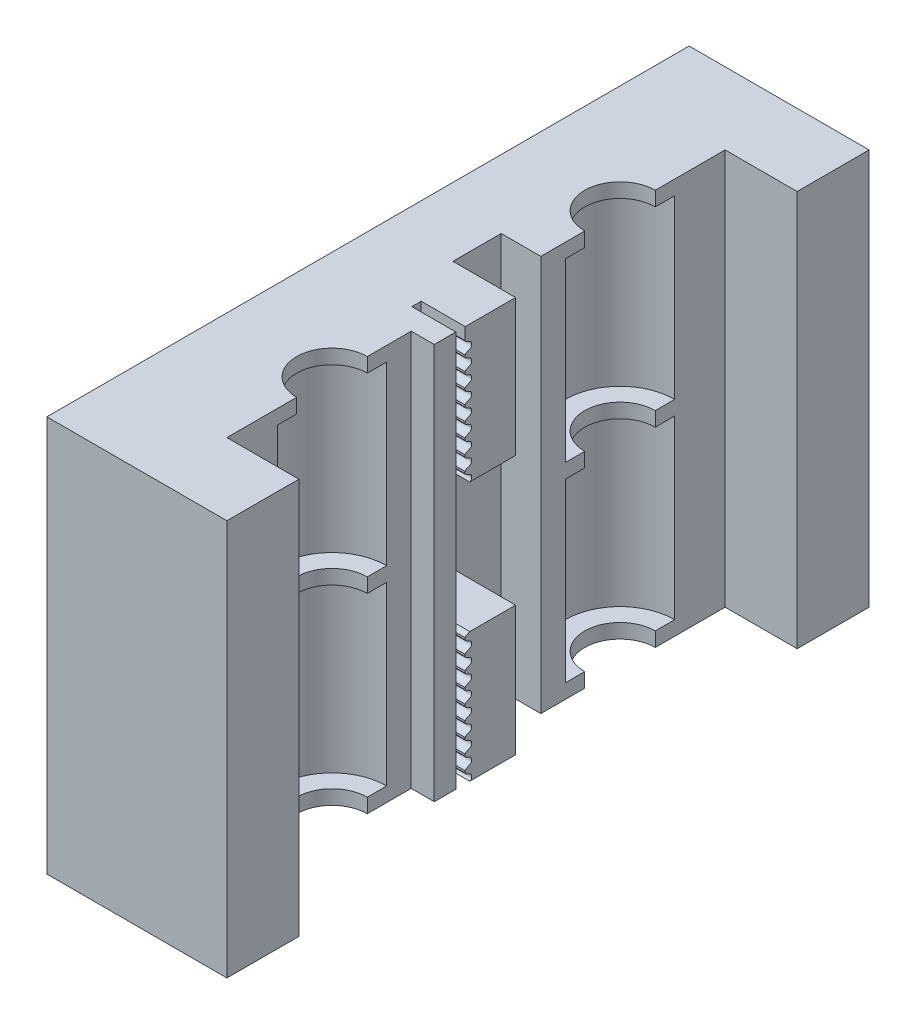
SolidWorks part; units mm, degrees
ref_plane "Front Plane" through (0, 0, 0) normal (0, 0, 1) x (1, 0, 0)
ref_plane "Top Plane" through (0, 0, 0) normal (0, 1, 0) x (1, 0, 0)
ref_plane "Right Plane" through (0, 0, 0) normal (1, 0, 0) x (0, 0, -1)
sketch "Sketch1" plane through (0, 0, 0) normal (0, 1, 0) x (1, 0, 0)
  line L0 (0, 36.6) -> (0, 43.6)
  line L1 (0, 43.6) -> (10, 43.6)
  line L2 (10, 43.6) -> (10, 53.6)
  line L3 (10, 53.6) -> (-15, 53.6)
  line L5 (-15, -35.6) -> (10, -35.6)
  line L6 (10, -35.6) -> (10, -25.6)
  line L7 (10, -25.6) -> (0, -25.6)
  line L8 (0, -25.6) -> (0, -18.6)
  line L9 (0, 21.4) -> (0, -3.4) construction
  line L10 (0, 18) -> (-5.5, 18)
  line L11 (-5.5, 18) -> (-5.5, 0)
  line L12 (-5.5, 0) -> (0, 0)
  line L24 (-15, 53.6) -> (-15, -35.6)
  line L25 (0, 0) -> (0, -3.4)
  line L26 (0, 18) -> (0, 21.4)
  arc A1 (0, 21.4) -> (0, 36.6) centre (0, 29) cw
  arc A2 (0, -18.6) -> (0, -3.4) centre (0, -11) cw
  dimension "D2" = 7.6
  dimension "D3" = 7.6
  dimension "D4" = 7
  dimension "D5" = 7
  dimension "D6" = 10
  dimension "D7" = 10
  dimension "D8" = 18
  dimension "D9" = 10
  dimension "D10" = 10
  dimension "D11" = 5.5
  dimension "D12" = 3.4
  dimension "D13" = 3.4
  dimension "D14" = 25
  dimension "D15" = 40
extrude "Boss-Extrude1" add sketch "Sketch1" along normal blind 55
sketch "Sketch2" plane through (0, 0, 0) normal (0, -1, 0) x (1, 0, 0)
  line L0 (0, 18.6) -> (0, 15.9)
  line L1 (0, 6.1) -> (0, 3.4)
  line L2 (0, -21.4) -> (0, -24.102)
  line L3 (0, -33.898) -> (0, -36.6)
  arc A0 (0, 3.4) -> (0, 18.6) centre (0, 11) cw
  arc A1 (0, 6.1) -> (0, 15.9) centre (0, 11) cw
  arc A2 (0, -36.6) -> (0, -21.4) centre (0, -29) cw
  arc A3 (0, -33.898) -> (0, -24.102) centre (0, -29) cw
  dimension "D1" = 4.9
  dimension "D2" = 4.898
extrude "Boss-Extrude2" add sketch "Sketch2" against normal blind 2
ref_plane "Plane1" through (0, 26.5, 0) normal (0, -1, 0) x (-1, 0, 0)
sketch "Sketch3" plane through (0, 26.5, 0) normal (0, -1, 0) x (-1, 0, 0)
  line L0 (0, -3.4) -> (0, -6.1)
  line L1 (0, -15.9) -> (0, -18.6)
  line L2 (0, 21.4) -> (0, 24.1)
  line L3 (0, 33.9) -> (0, 36.6)
  arc A0 (0, -18.6) -> (0, -3.4) centre (0, -11) ccw
  arc A1 (0, -15.9) -> (0, -6.1) centre (0, -11) ccw
  arc A2 (0, 36.6) -> (0, 21.4) centre (0, 29) cw
  arc A3 (0, 24.1) -> (0, 33.9) centre (0, 29) ccw
  dimension "D1" = 4.9
extrude "Boss-Extrude3" add sketch "Sketch3" against normal blind 2
ref_plane "Plane2" through (0, 53, 0) normal (0, -1, 0) x (-1, 0, 0)
sketch "Sketch4" plane through (0, 53, 0) normal (0, -1, 0) x (-1, 0, 0)
  line L0 (0, -18.6) -> (0, -15.9)
  line L1 (0, -6.1) -> (0, -3.4)
  line L2 (0, 36.6) -> (0, 33.9)
  line L3 (0, 24.1) -> (0, 21.4)
  arc A0 (0, -3.4) -> (0, -18.6) centre (0, -11) cw
  arc A1 (0, -15.9) -> (0, -6.1) centre (0, -11) ccw
  arc A2 (0, -15.9) -> (0, -6.1) centre (0, -11) ccw construction
  arc A3 (0, 21.4) -> (0, 36.6) centre (0, 29) ccw construction
  arc A5 (0, 24.1) -> (0, 33.9) centre (0, 29) ccw
  arc A6 (0, 21.4) -> (0, 36.6) centre (0, 29) ccw
  arc A7 (0, 24.1) -> (0, 33.9) centre (0, 29) ccw construction
extrude "Boss-Extrude4" add sketch "Sketch4" against normal blind 2
sketch "Sketch7" plane through (0, 55, 0) normal (0, 1, 0) x (1, 0, 0)
  line L0 (0, 0) -> (3.2, 0)
  line L1 (3.2, 0) -> (3.2, -2)
  line L2 (3.2, -2) -> (0, -2)
  line L3 (0, -6.1) -> (0, 0) construction
  line L4 (0, -2) -> (0, 0)
  dimension "D1" = 2
  dimension "D2" = 3.2
extrude "Boss-Extrude5" add sketch "Sketch7" against normal up to surface (55 mm away) up to face at (-0.6749, 0, -9)
sketch "Sketch8" plane through (0, 55, 0) normal (0, 1, 0) x (1, 0, 0)
  line L0 (0, 18) -> (0, 0) construction
  line L1 (-3.9424, 9) -> (6.0186, 9) construction
  line L2 (-5.5, 0) -> (3.2, 0)
  line L3 (3.2, 0) -> (-5.5, 0) construction
  line L4 (3.2, 0) -> (3.2, 3)
  line L5 (3.2, 3) -> (-5.5, 3)
  line L6 (-5.5, 0) -> (-5.5, 18) construction
  line L7 (-5.5, 3) -> (-5.5, 0)
  line L8 (3.2, -2) -> (3.2, 0) construction
  line L9 (-5.5, 11.3) -> (3.2, 11.3)
  line L10 (3.2, 11.3) -> (3.2, 4.3)
  line L11 (3.2, 4.3) -> (-5.5, 4.3)
  line L12 (-5.5, 4.3) -> (-5.5, 11.3)
  point P6 (0, 9)
  dimension "D1" = 3
  dimension "D2" = 7
  dimension "D3" = 1.3
extrude "Boss-Extrude6" add sketch "Sketch8" against normal up to surface (55 mm away) up to face at (-0.2443, 0, -7.7778)
sketch "Sketch11" plane through (3.2, 0, 0) normal (1, 0, 0) x (0, 0, -1)
  line L0 (1264.5675, 560.6102) -> (1262.5675, 560.6102) construction
  line L1 (4.3, 0) -> (4.3, 55) construction
  line L2 (4.2853, 45.4328) -> (4.2853, 47.4569)
  spline S0 degree 3 poles (4.2853, 47.4569) (4.284, 47.4147) (4.2867, 47.3463) (4.3158, 47.2523) (4.3712, 47.1708) (4.4771, 47.1012) (4.6041, 47.0544) (4.7214, 46.9971) (4.8254, 46.9474) (4.9241, 46.9047) (5.0186, 46.8525) (5.1086, 46.7783) (5.1561, 46.6816) (5.1905, 46.5926) (5.1913, 46.5195) (5.1931, 46.4561) (5.1891, 46.3829) (5.1871, 46.2871) (5.1399, 46.1709) (5.0494, 46.057) (4.9087, 45.9856) (4.7554, 45.916) (4.621, 45.8529) (4.5075, 45.8004) (4.4122, 45.7562) (4.3028, 45.6419) (4.2855, 45.5136) (4.2853, 45.4328) knots 0 0 0 0 0.042789 0.068472 0.09859 0.140403 0.193951 0.235463 0.272242 0.310543 0.344117 0.381404 0.42616 0.451184 0.477135 0.499165 0.515432 0.551275 0.595353 0.639476 0.695379 0.752126 0.810504 0.845135 0.878871 0.916023 1 1 1 1
  line M5 (4.3, 55) -> (4.3, 0)
  dimension "D1" = 2
extrude "Cut-Extrude4" cut sketch "Sketch11" against normal up to surface (8.7 mm away) contours S0 M5 region at (3.2, 46.4474, -4.673) up to face at (-5.5, 27.5, -3.65)
pattern_linear "LPattern1" count 24 spacing 2 along (0, -1, 0) count 4 spacing 2 along (0, 1, 0) of "Cut-Extrude4"
sketch "Sketch12" plane through (3.2, 0, 0) normal (1, 0, 0) x (0, 0, -1)
  line L0 (11.3, 0) -> (11.3, 55) construction
  line L1 (11.3, 36) -> (4.3, 36)
  line L2 (11.3, 36) -> (11.3, 18)
  line L3 (11.3, 18) -> (4.3, 18)
  line L4 (4.3, 36) -> (4.3, 18)
  dimension "D1" = 18
  dimension "D2" = 19
extrude "Cut-Extrude5" cut sketch "Sketch12" against normal up to surface (8.7 mm away) up to face at (-5.5, 27.5, -14.65)
sketch "Sketch13" plane through (0, 55, 0) normal (0, 1, 0) x (1, 0, 0)
  line L0 (-5.5, 3) -> (-2.9059, 3)
  line L1 (3.2, 3) -> (-5.5, 3) construction
  line L6 (-2.9059, 3) -> (-2.9059, 7.169)
  line L7 (-2.9059, 7.169) -> (-5.5, 7.169)
  line L8 (-5.5, 18) -> (-5.5, 0) construction
  line L9 (-5.5, 7.169) -> (-5.5, 3)
extrude "Boss-Extrude16" add sketch "Sketch13" against normal up to surface (55 mm away) up to face at (-0.409, 0, -8.1123)
sketch "Sketch14" plane through (0, 55, 0) normal (0, 1, 0) x (1, 0, 0)
  line L0 (0, 0) -> (0, -2)
  line L1 (0, -2) -> (3.2, -2)
  line L2 (3.2, -2) -> (3.2, 0)
  line L3 (3.2, -2) -> (3.2, 3) construction
  line L4 (3.2, 0) -> (0, 0)
extrude "Cut-Extrude6" cut sketch "Sketch14" against normal up to surface (55 mm away) up to face at (-0.1732, 0, -8.1123)
sketch "Sketch16" plane through (-2.9059, 0, 0) normal (1, 0, 0) x (0, 0, -1)
  line L0 (7.169, 36) -> (3, 36)
  line L1 (3, 0) -> (3, 55) construction
  line L2 (7.169, 18) -> (3, 18)
  line L3 (3, 18) -> (3, 36)
  line L4 (7.169, 36) -> (7.169, 18)
extrude "Cut-Extrude7" cut sketch "Sketch16" against normal up to surface (2.5941 mm away) up to face at (-5.5, 27.25, -11.9423)
